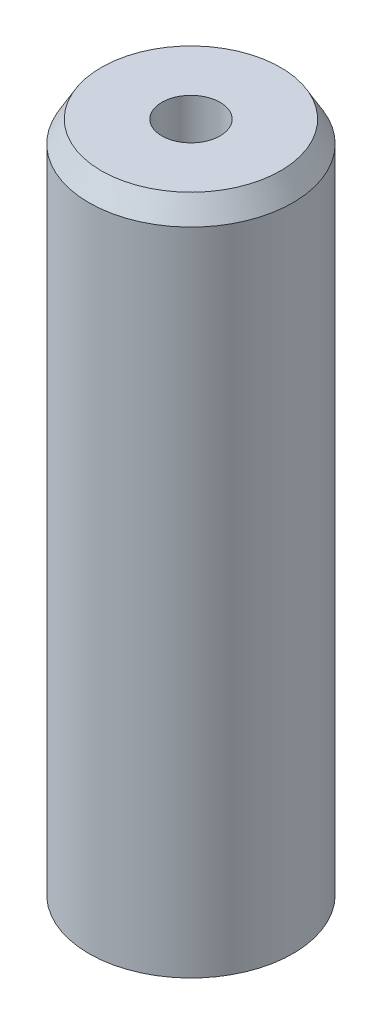
SolidWorks part; units mm, degrees
ref_plane "Front Plane" through (0, 0, 0) normal (0, 0, 1) x (1, 0, 0)
ref_plane "Top Plane" through (0, 0, 0) normal (0, 1, 0) x (1, 0, 0)
ref_plane "Right Plane" through (0, 0, 0) normal (1, 0, 0) x (0, 0, -1)
sketch "Sketch1" plane through (0, 0, 0) normal (0, 1, 0) x (1, 0, 0)
  circle A0 centre (0, 0) radius 10
  dimension "SHAFT_OD" = 20
extrude "Boss-Extrude1" add sketch "Sketch1" along normal blind 67.0809
sketch "Sketch2" plane through (0, 0, 0) normal (0, 1, 0) x (1, 0, 0)
  circle A0 centre (0, 0) radius 2.8579
  dimension "BORE_D" = 5.7157
extrude "Cut-Extrude1" cut sketch "Sketch2" along normal through all
chamfer "Chamfer1" distance 2.1026 angle 30 2 edges at (0, 67.0809, 10) (0, 0, 10) first distance on face at (0, 67.0809, 10) first distance on face at (0, 0, 2.8579)
